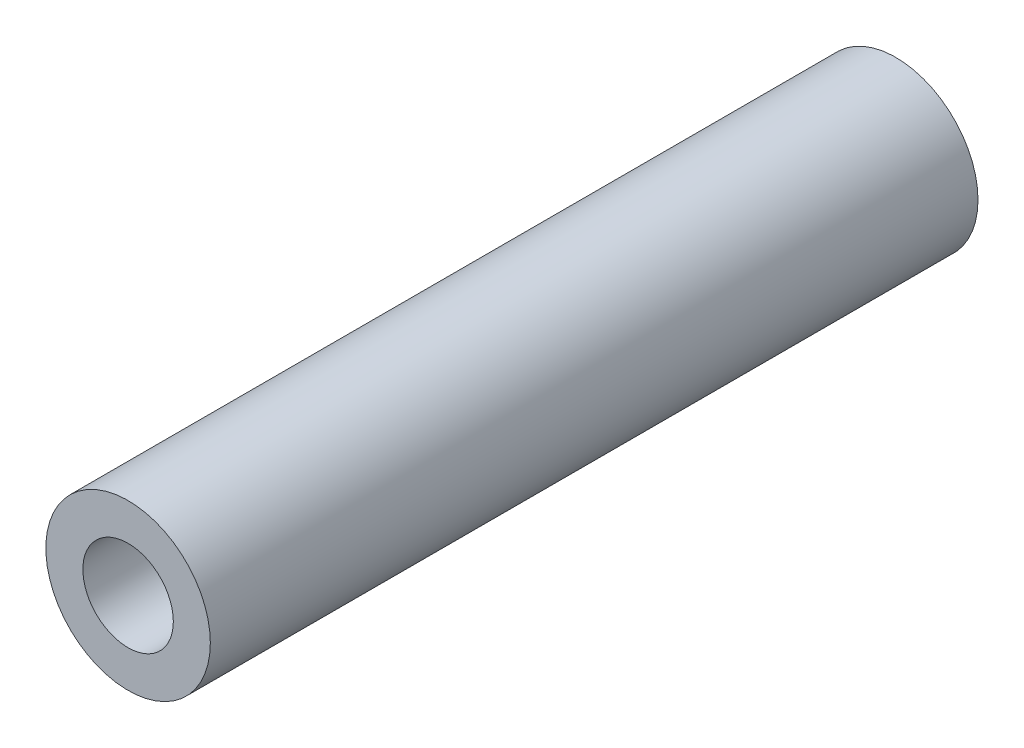
SolidWorks part; units mm, degrees
ref_plane "Płaszczyzna przednia" through (0, 0, 0) normal (0, 0, 1) x (1, 0, 0)
ref_plane "Płaszczyzna górna" through (0, 0, 0) normal (0, 1, 0) x (1, 0, 0)
ref_plane "Płaszczyzna prawa" through (0, 0, 0) normal (1, 0, 0) x (0, 0, -1)
sketch "Szkic1" plane through (0, 0, 0) normal (1, 0, 0) x (0, 0, -1)
  line L0 (-140, 0) -> (-140, 15)
  line L1 (-140, 15) -> (0, 15)
  line L2 (0, 15) -> (0, 0)
  line L3 (0, 0) -> (-140, 0)
  line L4 (0, 0) -> (-140, 0) construction
sketch "Szkic2" plane through (0, 0, 0) normal (1, 0, 0) x (0, 0, -1)
  line L0 (-140, 0) -> (-140, 8.25)
  line L1 (-140, 8.25) -> (0, 8.25)
  line L2 (0, 8.25) -> (0, 0)
  line L3 (0, 0) -> (-140, 0)
  line L4 (0, 0) -> (-140, 0) construction
revolve "Obrót1" add sketch "Szkic1" angle 360 about L4 reverse direction yes
revolve "Wycięcie-obrót1" cut sketch "Szkic2" angle 360 about L4 reverse direction yes
ref_plane "Płaszczyzna1" through (0, 0, 140) normal (0, 0, 1) x (1, 0, 0)
ref_plane "IP2 XY" through (0, 0, 140) normal (0, 0, 1) x (1, 0, 0)
ref_plane "IP2 XZ" through (0, 0, 0) normal (0, -1, 0) x (-1, 0, 0)
ref_plane "IP2 YZ" through (0, 0, 0) normal (1, 0, 0) x (0, 0, -1)
ref_axis "IP2 X" through (-80.9, 0, 140) along (1, 0, 0)
ref_axis "IP2 Y" through (0, -50, 140) along (0, 1, 0)
ref_axis "IP2 Z" through (0, 0, 80.9) along (0, 0, -1)
sketch3d "IP2"
  point P0 (0, 0, 140)
ref_plane "IP1 XY" through (0, 0, 0) normal (0, 0, 1) x (1, 0, 0)
ref_plane "IP1 XZ" through (0, 0, 0) normal (0, -1, 0) x (-1, 0, 0)
ref_plane "IP1 YZ" through (0, 0, 0) normal (1, 0, 0) x (0, 0, -1)
ref_axis "IP1 X" through (-80.9, 0, 0) along (1, 0, 0)
ref_axis "IP1 Y" through (0, -50, 0) along (0, 1, 0)
ref_axis "IP1 Z" through (0, 0, 80.9) along (0, 0, -1)
sketch3d "IP1"
  point P0 (0, 0, 0)
